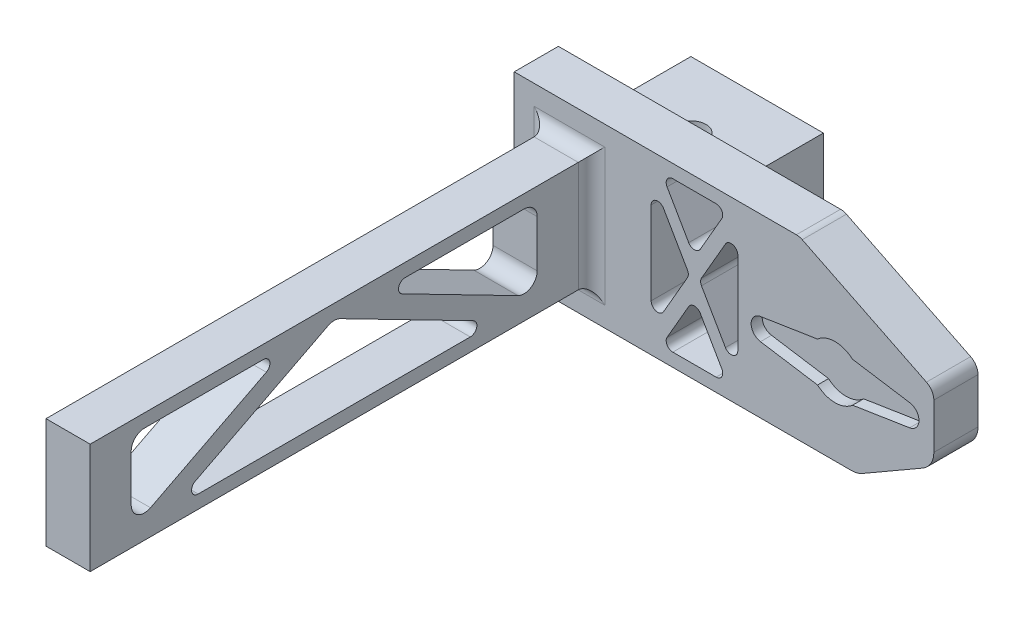
SolidWorks part; units mm, degrees
material "PLA"
ref_plane "Front Plane" through (0, 0, 0) normal (0, 0, 1) x (1, 0, 0)
ref_plane "Top Plane" through (0, 0, 0) normal (0, 1, 0) x (1, 0, 0)
ref_plane "Right Plane" through (0, 0, 0) normal (1, 0, 0) x (0, 0, -1)
sketch "Sketch3" plane through (0, 0, 0) normal (0, 0, 1) x (1, 0, 0)
  line L1 (-22.6388, -7.4411) -> (22.3612, -7.4411)
  line L2 (-22.6388, -7.4411) -> (-22.6388, 7.5589)
  line L3 (-22.6388, 7.5589) -> (22.3612, 7.5589)
  line L4 (22.3612, -7.4411) -> (22.3612, 7.5589)
  dimension "D1" = 15
  dimension "D2" = 45
extrude "Boss-Extrude1" add sketch "Sketch3" against normal blind 10
sketch "Sketch2" plane through (0, 0, 0) normal (0, 0, 1) x (1, 0, 0)
  line L0 (-16.8881, 2.4697) -> (-3.9686, 4.5)
  line L1 (-16.8881, -2.4697) -> (-3.9686, -4.5)
  line L2 (3.9686, 4.5) -> (16.8881, 2.4697)
  line L3 (16.8881, -2.4697) -> (3.9686, -4.5)
  arc A0 (-16.8881, 2.4697) -> (-16.8881, -2.4697) centre (-16.5, 0) ccw
  arc A1 (-3.9686, 4.5) -> (3.9686, 4.5) centre (0, 0) cw
  arc A2 (-3.9686, -4.5) -> (3.9686, -4.5) centre (0, 0) ccw
  arc A3 (16.8881, -2.4697) -> (16.8881, 2.4697) centre (16.5, 0) ccw
extrude "Cut-Extrude1" cut sketch "Sketch2" against normal blind 2.5
sketch "Sketch11" plane through (0, -7.4411, 0) normal (0, -1, 0) x (1, 0, 0)
  line L0 (8.25, 0) -> (-8.25, 0) construction
  line L1 (22.3612, -10) -> (-22.6388, -10)
  line L2 (22.3612, -10) -> (22.3612, 0)
  line L3 (22.3612, 0) -> (-22.6388, 0)
  line L4 (-22.6388, -10) -> (-22.6388, 0)
  line L5 (-22.6388, -10) -> (-22.6388, 0) construction
extrude "Boss-Extrude5" add sketch "Sketch11" along normal blind 10
sketch "Sketch14" plane through (0, 7.5589, 0) normal (0, 1, 0) x (1, 0, 0)
  line L0 (-8.25, 0) -> (8.25, 0) construction
  line L1 (22.3612, 10) -> (-22.6388, 10)
  line L2 (22.3612, 10) -> (22.3612, 0)
  line L3 (22.3612, 0) -> (-22.6388, 0)
  line L4 (-22.6388, 10) -> (-22.6388, 0)
  line L5 (-22.6388, 10) -> (-22.6388, 0) construction
extrude "Boss-Extrude7" add sketch "Sketch14" along normal blind 15
sketch "Sketch20" plane through (-22.6388, 0, 0) normal (-1, 0, 0) x (0, 0, 1)
  line L0 (0, -22) -> (0, 22) construction
  line L1 (-10, 22.5589) -> (0, 22.5589)
  line L2 (-10, 22.5589) -> (-10, -17.4411)
  line L3 (-10, -17.4411) -> (0, -17.4411)
  line L4 (0, 22.5589) -> (0, -17.4411)
  line L5 (0, -17.4411) -> (-10, -17.4411) construction
extrude "Boss-Extrude10" add sketch "Sketch20" along normal blind 50
sketch "Sketch21" plane through (0, 0, 0) normal (0, 0, 1) x (1, 0, 0)
  line L1 (-65.1388, 15.0589) -> (-55.1388, 15.0589)
  line L2 (-65.1388, 15.0589) -> (-65.1388, -9.9411)
  line L3 (-65.1388, -9.9411) -> (-55.1388, -9.9411)
  line L4 (-55.1388, 15.0589) -> (-55.1388, -9.9411)
  line L5 (-72.6388, 22.5589) -> (22.3612, 22.5589) construction
  line L6 (-72.6388, -17.4411) -> (-72.6388, 22.5589) construction
  dimension "D1" = 7.5
  dimension "D2" = 25
  dimension "D3" = 7.5
  dimension "D4" = 10
extrude "Boss-Extrude11" add sketch "Sketch21" along normal blind 113.5
sketch "Sketch22" plane through (0, 0, -10) normal (0, 0, -1) x (-1, 0, 0)
  line L0 (72.6388, 22.5589) -> (72.6388, -17.4411) construction
  line L1 (42.6388, 5.5589) -> (72.6388, 5.5589)
  line L2 (42.6388, 5.5589) -> (42.6388, -0.4411)
  line L3 (42.6388, -0.4411) -> (72.6388, -0.4411)
  line L4 (72.6388, 5.5589) -> (72.6388, -0.4411)
  line L5 (42.6388, 5.5589) -> (72.6388, -0.4411) construction
  line L6 (42.6388, -0.4411) -> (72.6388, 5.5589) construction
  line L7 (72.6388, -17.4411) -> (-22.3612, -17.4411) construction
  point P0 (57.6388, 2.5589)
  dimension "D1" = 20
  dimension "D2" = 30
  dimension "D3" = 6
extrude "Boss-Extrude12" add sketch "Sketch22" along normal blind 30
sketch "Sketch23" plane through (0, -0.4411, 0) normal (0, -1, 0) x (1, 0, 0)
  line L1 (-72.6388, -10) -> (-42.6388, -10)
  line L2 (-72.6388, -10) -> (-72.6388, -40)
  line L3 (-72.6388, -40) -> (-42.6388, -40)
  line L4 (-42.6388, -10) -> (-42.6388, -40)
extrude "Boss-Extrude13" add sketch "Sketch23" along normal blind 8.5
fillet "Fillet1" radius 3 4 edges at (-60.1388, 15.0589, 0) (-65.1388, 2.5589, 0) (-55.1388, 2.5589, 0) (-60.1388, -9.9411, 0)
chamfer "Chamfer1" distance 15 angle 63.75 1 edges at (22.3612, 22.5589, -5) first distance on face at (22.3612, 2.5589, -5)
fillet "Fillet2" radius 3 2 edges at (-8.0558, 22.5589, -5) (22.3612, 7.5589, -5)
chamfer "Chamfer2" distance 10 angle 60 1 edges at (22.3612, -17.4411, -5) first distance on face at (22.3612, -5.8739, -5)
fillet "Fillet3" radius 5 2 edges at (5.0406, -17.4411, -5) (22.3612, -7.4411, -5)
sketch "Sketch24" plane through (-65.1388, 0, 0) normal (-1, 0, 0) x (0, 0, 1)
  line L0 (58.25, 15.0589) -> (58.25, -9.9411) construction
  line L1 (113.5, 15.0589) -> (3, 15.0589) construction
  line L2 (113.5, -9.9411) -> (3, -9.9411) construction
  line L3 (58.25, -6.9411) -> (95.25, -6.9411)
  line L4 (58.25, -6.9411) -> (21.25, -6.9411)
  line L5 (21.25, -6.9411) -> (58.25, 12.0589)
  line L6 (58.25, 12.0589) -> (95.25, -6.9411)
  line L7 (48.399, 12.0589) -> (12.29, -6.4835)
  line L8 (48.399, 12.0589) -> (12.29, 12.0589)
  line L9 (12.29, 12.0589) -> (12.29, -6.4835)
  line L10 (68.101, 12.0589) -> (104.21, 12.0589)
  line L11 (68.101, 12.0589) -> (104.21, -6.4835)
  line L12 (104.21, 12.0589) -> (104.21, -6.4835)
  dimension "D1" = 37
  dimension "D2" = 37
  dimension "D3" = 3
  dimension "D4" = 3
  dimension "D5" = 3
  dimension "D6" = 4.5
  dimension "D7" = 18.5424
extrude "Cut-Extrude2" cut sketch "Sketch24" against normal through all
fillet "Fillet4" radius 3 5 edges at (-60.1388, -6.4835, 12.29) (-60.1388, 12.0589, 12.29) (-60.1388, -6.4835, 104.21) (-60.1388, 12.0589, 104.21) (-60.1388, 12.0589, 58.25)
fillet "Fillet5" radius 1.5 4 edges at (-60.1388, 12.0589, 68.101) (-60.1388, -6.9411, 95.25) (-60.1388, -6.9411, 21.25) (-60.1388, 12.0589, 48.399)
sketch "Sketch30" plane through (0, 5.5589, 0) normal (0, 1, 0) x (1, 0, 0)
  line L0 (-72.6388, 40) -> (-42.6388, 10) construction
  line L1 (-42.6388, 40) -> (-72.6388, 10) construction
  point P10 (-57.6388, 25)
hole_wizard "M8 Tapped Hole1" positions "Sketch30" profile "Sketch31" tap size "M8" standard "ISO"
sketch "Sketch31" plane through (-57.6388, 5.5589, -25) normal (1, 0, 0) x (0, 0, 1)
  line L0 (0, 0) -> (0, 24.2929)
  line L1 (0, 24.2929) -> (3.4, 22.25)
  line L2 (3.4, 22.25) -> (3.4, 0)
  line L5 (3.4, 0) -> (0, 0)
  line L10 (0, 24.2929) -> (-3.4, 22.25) construction
  line L11 (0, -6.35) -> (0, 107.95) construction
  dimension "Tap Drill Dia." = 6.8
  dimension "Tap Drill Depth" = 22.25
  dimension "Drill Angle" = 118
cosmetic thread "Hole Thread1" parameters "D1"=16, "D2"=8
ref_plane "Plane1" through (-42.6388, 5.5589, -10) normal (0, 0, 1) x (1, 0, 0)
sketch "Sketch32" plane through (-42.6388, 5.5589, -10) normal (0, 0, 1) x (1, 0, 0)
  line L0 (33.8835, 17) -> (-30, 17) construction
  line L1 (1, 14) -> (20.6191, 14) construction
  line L2 (1, 14) -> (1, -20) construction
  line L3 (1, -20) -> (20.6191, -20) construction
  line L4 (20.6191, 14) -> (20.6191, -20) construction
  line L5 (-30, -23) -> (46.3397, -23) construction
  line L6 (0, 0) -> (0, -14.5) construction
  line L7 (20.6191, 14) -> (1, -20) construction
  line L8 (20.6191, -20) -> (1, 14) construction
  line L9 (10.8096, 14) -> (3.3096, 14)
  line L10 (3.3096, 14) -> (10.8096, 1.0025)
  line L11 (10.8096, 1.0025) -> (18.3096, 14)
  line L12 (18.3096, 14) -> (10.8096, 14)
  line L13 (1, 12) -> (9.6555, -3)
  line L14 (9.6555, -3) -> (1, -18)
  line L15 (1, -18) -> (1, -3)
  line L16 (1, -3) -> (1, 12)
  line L17 (20.6191, -3) -> (1, -3) construction
  line L18 (10.8096, -20) -> (10.8096, 14) construction
  line L19 (10.8096, -7.0025) -> (18.3096, -20)
  line L20 (3.3096, -20) -> (10.8096, -7.0025)
  line L21 (10.8096, -20) -> (3.3096, -20)
  line L22 (18.3096, -20) -> (10.8096, -20)
  line L23 (20.6191, -18) -> (20.6191, -3)
  line L24 (11.9636, -3) -> (20.6191, -18)
  line L25 (20.6191, 12) -> (11.9636, -3)
  line L26 (20.6191, -3) -> (20.6191, 12)
  dimension "D1" = 3
  dimension "D2" = 3
  dimension "D3" = 1
  dimension "D4" = 7.5
  dimension "D5" = 7.5
  dimension "D6" = 3
  dimension "D7" = 15
  dimension "D8" = 15
extrude "Cut-Extrude3" cut sketch "Sketch32" along normal through all
fillet "Fillet6" radius 1.5 12 edges at (-41.6388, 17.5589, -5) (-31.8293, 6.5614, -5) (-39.3293, 19.5589, -5) (-24.3293, 19.5589, -5) (-22.0197, -12.4411, -5) (-22.0197, 17.5589, -5) (-30.6752, 2.5589, -5) (-39.3293, -14.4411, -5) (-24.3293, -14.4411, -5) (-31.8293, -1.4436, -5) (-41.6388, -12.4411, -5) (-32.9834, 2.5589, -5)
